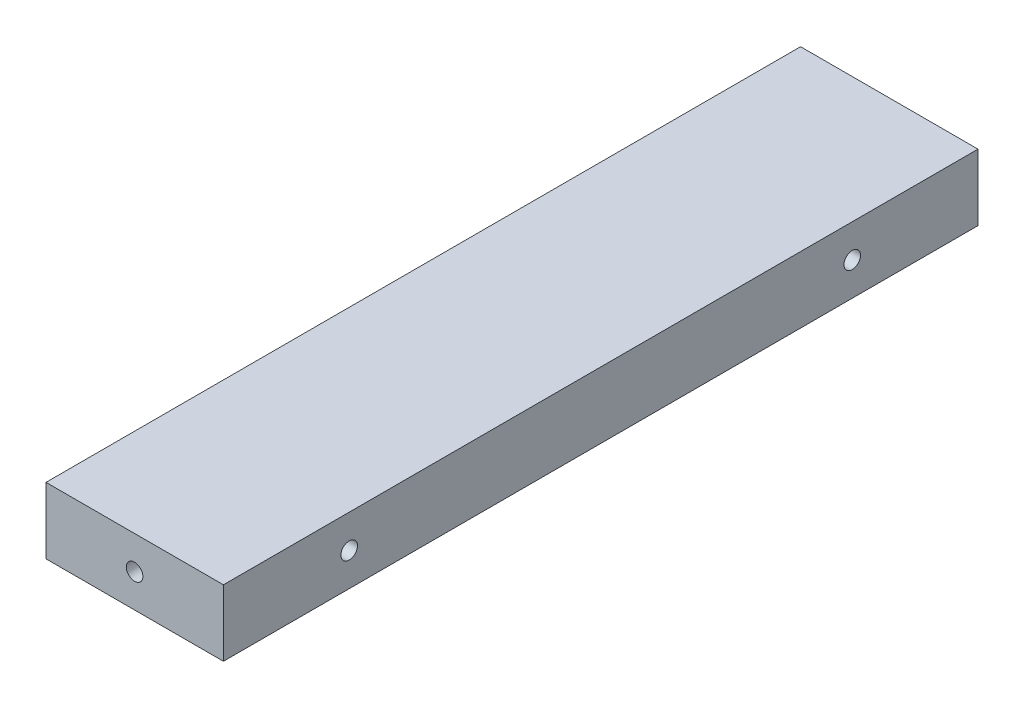
SolidWorks part; units mm, degrees
material "Beech"
ref_plane "Front Plane" through (0, 0, 0) normal (0, 0, 1) x (1, 0, 0)
ref_plane "Top Plane" through (0, 0, 0) normal (0, 1, 0) x (1, 0, 0)
ref_plane "Right Plane" through (0, 0, 0) normal (1, 0, 0) x (0, 0, -1)
sketch "Sketch1" plane through (0, 0, 0) normal (0, 0, 1) x (1, 0, 0)
  line L0 (-6.0809, -132.7) -> (-6.0809, 132.7) construction
  line L1 (-40.0809, -120) -> (-6.0809, -120)
  line L2 (-40.0809, -120) -> (-40.0809, -132.7)
  line L3 (-40.0809, -132.7) -> (-6.0809, -132.7)
  line L4 (-6.0809, -120) -> (-6.0809, -132.7)
  dimension "D1" = 12.7
extrude "Boss-Extrude1" add sketch "Sketch1" along normal up to surface (144.6 mm away)
hole_wizard "Hole1" positions "Sketch2" profile "Sketch3" legacy
sketch "Sketch2" plane through (12.9191, 0, 66.1243) normal (1, 0, 0) x (0, -1, 0)
  line L21 (0, 20.1243) -> (0, 66.1243) construction
  point P37 (126.35, 72.4743)
  point P42 (146.0833, -84.8257)
  point P44 (172.1667, -84.8257)
  point P63 (126.35, -54.3757)
  point P65 (126.35, 42.0243)
  point P76 (-172.1667, -84.8257)
  point P77 (-146.0833, -84.8257)
  point P78 (-126.35, -54.3757)
  point P79 (-126.35, 42.0243)
  point P80 (-126.35, 72.4743)
sketch "Sketch3" plane through (12.9191, -126.35, -6.35) normal (0, 1, 0) x (0, 0, -1)
  line L0 (0, 0) -> (0, 32.7039)
  line L1 (0, 32.7039) -> (1.5875, 31.75)
  line L2 (1.5875, 31.75) -> (1.5875, 4.0177)
  line L3 (1.5875, 4.0177) -> (5.08, 0)
  line L4 (5.08, 0) -> (0, 0)
  line L5 (0, -14.3089) -> (0, 102.4216) construction
  line L6 (0, 32.7039) -> (-1.5875, 31.75) construction
  line L7 (-1.5875, 4.0177) -> (-5.08, 0) construction
  dimension "Diameter" = 3.175
  dimension "Depth" = 31.75
  dimension "C-Sink Diameter" = 10.16
  dimension "C-Sink Angle" = 82
  dimension "Drill Angle" = 118
hole_wizard "Hole2" positions "Sketch4" profile "Sketch5" legacy
sketch "Sketch4" plane through (12.9191, 0, 78.4757) normal (1, 0, 0) x (0, 1, 0)
  line L21 (0, 20.1243) -> (0, 66.1243) construction
  point P37 (126.35, 72.4743)
  point P42 (146.0833, -84.8257)
  point P44 (172.1667, -84.8257)
  point P63 (126.35, -54.3757)
  point P65 (126.35, 42.0243)
  point P76 (-172.1667, -84.8257)
  point P77 (-146.0833, -84.8257)
  point P78 (-126.35, -54.3757)
  point P79 (-126.35, 42.0243)
  point P80 (-126.35, 72.4743)
sketch "Sketch5" plane through (12.9191, 126.35, 150.95) normal (0, 1, 0) x (0, 0, -1)
  line L0 (0, 0) -> (0, 32.7039)
  line L1 (0, 32.7039) -> (1.5875, 31.75)
  line L2 (1.5875, 31.75) -> (1.5875, 4.0177)
  line L3 (1.5875, 4.0177) -> (5.08, 0)
  line L4 (5.08, 0) -> (0, 0)
  line L5 (0, -14.3089) -> (0, 102.4216) construction
  line L6 (0, 32.7039) -> (-1.5875, 31.75) construction
  line L7 (-1.5875, 4.0177) -> (-5.08, 0) construction
  dimension "Diameter" = 3.175
  dimension "Depth" = 31.75
  dimension "C-Sink Diameter" = 10.16
  dimension "C-Sink Angle" = 82
  dimension "Drill Angle" = 118
hole_wizard "Hole5" positions "Sketch8" profile "Sketch9" legacy
sketch "Sketch8" plane through (-195.3677, 0, 157.3) normal (0, 0, 1) x (0, -1, 0)
  line L0 (120, 172.2617) -> (217.3, 172.2617) construction
  point P8 (126.35, 172.2617)
  point P10 (207.775, 172.2617)
sketch "Sketch9" plane through (-23.1059, -207.775, 157.3) normal (1, 0, 0) x (0, -1, 0)
  line L0 (0, 0) -> (0, 32.7039)
  line L1 (0, 32.7039) -> (1.5875, 31.75)
  line L2 (1.5875, 31.75) -> (1.5875, 4.0177)
  line L3 (1.5875, 4.0177) -> (5.08, 0)
  line L4 (5.08, 0) -> (0, 0)
  line L5 (0, -14.3089) -> (0, 102.4216) construction
  line L6 (0, 32.7039) -> (-1.5875, 31.75) construction
  line L7 (-1.5875, 4.0177) -> (-5.08, 0) construction
  dimension "Diameter" = 3.175
  dimension "Depth" = 31.75
  dimension "C-Sink Diameter" = 10.16
  dimension "C-Sink Angle" = 82
  dimension "Drill Angle" = 118
hole_wizard "Hole6" positions "Sketch10" profile "Sketch11" legacy
sketch "Sketch10" plane through (-52.7809, 0, 78.4757) normal (-1, 0, 0) x (0, -1, 0)
  line L12 (0, 0) -> (0, 66.1243) construction
  line L17 (120, -84.8257) -> (217.3, -84.8257) construction
  line L21 (-217.3, -84.8257) -> (-120, -84.8257) construction
  point P0 (-207.775, 244.1214)
  point P3 (-207.775, 136.589)
  point P6 (-207.775, 48.5243)
  point P9 (-185.55, -84.8257)
  point P12 (-151.75, -84.8257)
  point P15 (-94.6, 72.4743)
  point P21 (94.6, 72.4743)
  point P24 (151.75, -84.8257)
  point P27 (185.55, -84.8257)
  point P30 (207.775, 48.5243)
  point P33 (207.775, 136.589)
  point P36 (207.775, 244.1214)
  point P39 (166.7958, 213.0704)
  point P42 (40.9792, 213.0704)
  point P45 (-40.9792, 213.0704)
  point P48 (-166.7958, 213.0704)
  point P51 (0, 104.2243)
  point P54 (0, 213.0704)
  point P57 (0, 323.4664)
  point P80 (-126.35, 34.5243)
  point P82 (-126.35, -46.8757)
  point P96 (126.35, -46.8757)
  point P97 (126.35, 34.5243)
  dimension "D4" = 31.75
  dimension "D5" = 31.75
sketch "Sketch11" plane through (-52.7809, 207.775, 322.5971) normal (0, 1, 0) x (0, 0, 1)
  line L0 (0, 0) -> (0, 32.7039)
  line L1 (0, 32.7039) -> (1.5875, 31.75)
  line L2 (1.5875, 31.75) -> (1.5875, 4.0177)
  line L3 (1.5875, 4.0177) -> (5.08, 0)
  line L4 (5.08, 0) -> (0, 0)
  line L5 (0, -14.3089) -> (0, 102.4216) construction
  line L6 (0, 32.7039) -> (-1.5875, 31.75) construction
  line L7 (-1.5875, 4.0177) -> (-5.08, 0) construction
  dimension "Diameter" = 3.175
  dimension "Depth" = 31.75
  dimension "C-Sink Diameter" = 10.16
  dimension "C-Sink Angle" = 82
  dimension "Drill Angle" = 118
hole_wizard "Hole7" positions "Sketch12" profile "Sketch13" legacy
sketch "Sketch12" plane through (-52.7809, 0, 66.1243) normal (-1, 0, 0) x (0, 1, 0)
  line L12 (0, 0) -> (0, 66.1243) construction
  line L17 (120, -84.8257) -> (217.3, -84.8257) construction
  line L21 (-217.3, -84.8257) -> (-120, -84.8257) construction
  point P0 (-207.775, 244.1214)
  point P3 (-207.775, 136.589)
  point P6 (-207.775, 48.5243)
  point P9 (-185.55, -84.8257)
  point P12 (-151.75, -84.8257)
  point P15 (-94.6, 72.4743)
  point P21 (94.6, 72.4743)
  point P24 (151.75, -84.8257)
  point P27 (185.55, -84.8257)
  point P30 (207.775, 48.5243)
  point P33 (207.775, 136.589)
  point P36 (207.775, 244.1214)
  point P39 (166.7958, 213.0704)
  point P42 (40.9792, 213.0704)
  point P45 (-40.9792, 213.0704)
  point P48 (-166.7958, 213.0704)
  point P51 (0, 104.2243)
  point P54 (0, 213.0704)
  point P57 (0, 323.4664)
  point P80 (-126.35, 34.5243)
  point P82 (-126.35, -46.8757)
  point P96 (126.35, -46.8757)
  point P97 (126.35, 34.5243)
  dimension "D4" = 31.75
  dimension "D5" = 31.75
sketch "Sketch13" plane through (-52.7809, -207.775, -177.9971) normal (0, 1, 0) x (0, 0, 1)
  line L0 (0, 0) -> (0, 32.7039)
  line L1 (0, 32.7039) -> (1.5875, 31.75)
  line L2 (1.5875, 31.75) -> (1.5875, 4.0177)
  line L3 (1.5875, 4.0177) -> (5.08, 0)
  line L4 (5.08, 0) -> (0, 0)
  line L5 (0, -14.3089) -> (0, 102.4216) construction
  line L6 (0, 32.7039) -> (-1.5875, 31.75) construction
  line L7 (-1.5875, 4.0177) -> (-5.08, 0) construction
  dimension "Diameter" = 3.175
  dimension "Depth" = 31.75
  dimension "C-Sink Diameter" = 10.16
  dimension "C-Sink Angle" = 82
  dimension "Drill Angle" = 118
